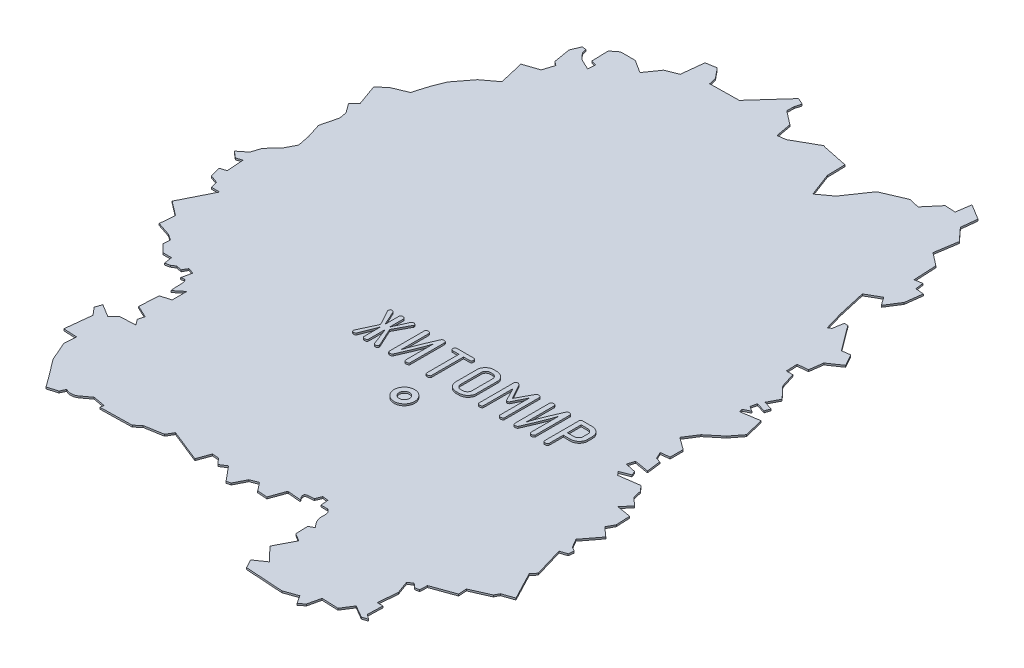
SolidWorks part; units mm, degrees
ref_plane "Спереди" through (0, 0, 0) normal (0, 0, 1) x (1, 0, 0)
ref_plane "Сверху" through (0, 0, 0) normal (0, 1, 0) x (1, 0, 0)
ref_plane "Справа" through (0, 0, 0) normal (1, 0, 0) x (0, 0, -1)
sketch "Эскиз1" plane through (0, 0, 0) normal (0, 1, 0) x (1, 0, 0)
  line B0 (-4547.6465, 8104.5812) -> (-4546.3562, 8148.7162)
  line B1 (-4546.3562, 8148.7162) -> (-4563.2116, 8148.7162)
  line B2 (-4563.2116, 8148.7162) -> (-4558.0351, 8205.1677)
  line B3 (-4558.0351, 8205.1677) -> (-4571.6622, 8242.8055)
  line B4 (-4571.6622, 8242.8055) -> (-4558.0351, 8251.2484)
  line B5 (-4558.0351, 8251.2484) -> (-4546.3562, 8240.8674)
  line B6 (-4546.3562, 8240.8674) -> (-4534.0321, 8242.8055)
  line B7 (-4534.0321, 8242.8055) -> (-4532.7265, 8264.8654)
  line B8 (-4532.7265, 8264.8654) -> (-4465.8915, 8288.8887)
  line B9 (-4465.8915, 8288.8887) -> (-4467.8422, 8312.9018)
  line B10 (-4467.8422, 8312.9018) -> (-4413.3211, 8336.9048)
  line B11 (-4413.3211, 8336.9048) -> (-4406.1913, 8350.5294)
  line B12 (-4406.1913, 8350.5294) -> (-4372.4474, 8362.2159)
  line B13 (-4372.4474, 8362.2159) -> (-4414.6267, 8442.6857)
  line B14 (-4414.6267, 8442.6857) -> (-4402.9274, 8457.6006)
  line B15 (-4402.9274, 8457.6006) -> (-4428.2385, 8543.2722)
  line B16 (-4428.2385, 8543.2722) -> (-4408.1294, 8549.7619)
  line B17 (-4408.1294, 8549.7619) -> (-4406.1913, 8565.3372)
  line B18 (-4406.1913, 8565.3372) -> (-4418.5154, 8572.4695)
  line B19 (-4418.5154, 8572.4695) -> (-4433.4227, 8597.7755)
  line B20 (-4433.4227, 8597.7755) -> (-4395.8078, 8647.1023)
  line B21 (-4395.8078, 8647.1023) -> (-4423.0442, 8671.113)
  line B22 (-4423.0442, 8671.113) -> (-4411.378, 8693.1729)
  line B23 (-4411.378, 8693.1729) -> (-4413.3211, 8734.0618)
  line B24 (-4413.3211, 8734.0618) -> (-4455.508, 8741.2017)
  line B25 (-4455.508, 8741.2017) -> (-4432.1451, 8766.5001)
  line B26 (-4432.1451, 8766.5001) -> (-4455.508, 8789.2153)
  line B27 (-4455.508, 8789.2153) -> (-4460.6921, 8812.5884)
  line B28 (-4460.6921, 8812.5884) -> (-4474.3319, 8828.1586)
  line B29 (-4474.3319, 8828.1586) -> (-4534.0321, 8819.7233)
  line B30 (-4534.0321, 8819.7233) -> (-4543.105, 8830.1119)
  line B31 (-4543.105, 8830.1119) -> (-4513.895, 8841.7756)
  line B32 (-4513.895, 8841.7756) -> (-4519.0994, 8854.1174)
  line B33 (-4519.0994, 8854.1174) -> (-4549.5947, 8860.5843)
  line B34 (-4549.5947, 8860.5843) -> (-4543.105, 8881.3488)
  line B35 (-4543.105, 8881.3488) -> (-4501.576, 8874.2393)
  line B36 (-4501.576, 8874.2393) -> (-4506.7576, 8915.1054)
  line B37 (-4506.7576, 8915.1054) -> (-4520.3974, 8919.0068)
  line B38 (-4520.3974, 8919.0068) -> (-4529.4626, 8939.1261)
  line B39 (-4529.4626, 8939.1261) -> (-4503.5318, 8942.385)
  line B40 (-4503.5318, 8942.385) -> (-4503.5318, 8979.9973)
  line B41 (-4503.5318, 8979.9973) -> (-4539.2061, 9005.9662)
  line B42 (-4539.2061, 9005.9662) -> (-4515.2081, 9043.5989)
  line B43 (-4515.2081, 9043.5989) -> (-4474.3319, 9077.3479)
  line B44 (-4474.3319, 9077.3479) -> (-4449.0208, 9109.7913)
  line B45 (-4449.0208, 9109.7913) -> (-4462.6403, 9166.2504)
  line B46 (-4462.6403, 9166.2504) -> (-4517.1462, 9157.8049)
  line B47 (-4517.1462, 9157.8049) -> (-4519.0994, 9167.5534)
  line B48 (-4519.0994, 9167.5534) -> (-4500.2755, 9176.6314)
  line B49 (-4500.2755, 9176.6314) -> (-4515.2081, 9186.3621)
  line B50 (-4515.2081, 9186.3621) -> (-4510.659, 9203.8805)
  line B51 (-4510.659, 9203.8805) -> (-4483.3997, 9195.4502)
  line B52 (-4483.3997, 9195.4502) -> (-4478.208, 9210.3778)
  line B53 (-4478.208, 9210.3778) -> (-4503.5318, 9218.8233)
  line B54 (-4503.5318, 9218.8233) -> (-4486.656, 9251.2363)
  line B55 (-4486.656, 9251.2363) -> (-4519.0994, 9285.6609)
  line B56 (-4519.0994, 9285.6609) -> (-4532.7265, 9328.4853)
  line B57 (-4532.7265, 9328.4853) -> (-4551.5403, 9328.4853)
  line B58 (-4551.5403, 9328.4853) -> (-4552.8459, 9360.9185)
  line B59 (-4552.8459, 9360.9185) -> (-4522.3354, 9364.1774)
  line B60 (-4522.3354, 9364.1774) -> (-4517.1462, 9403.141)
  line B61 (-4517.1462, 9403.141) -> (-4479.5034, 9429.0591)
  line B62 (-4479.5034, 9429.0591) -> (-4498.3324, 9462.831)
  line B63 (-4498.3324, 9462.831) -> (-4522.3354, 9459.5798)
  line B64 (-4522.3354, 9459.5798) -> (-4576.8463, 9532.8969)
  line B65 (-4576.8463, 9532.8969) -> (-4587.24, 9532.8969)
  line B66 (-4587.24, 9532.8969) -> (-4592.4191, 9502.4016)
  line B67 (-4592.4191, 9502.4016) -> (-4600.8595, 9497.2175)
  line B68 (-4600.8595, 9497.2175) -> (-4616.4348, 9550.4102)
  line B69 (-4616.4348, 9550.4102) -> (-4635.2536, 9633.4809)
  line B70 (-4635.2536, 9633.4809) -> (-4595.6753, 9656.2012)
  line B71 (-4595.6753, 9656.2012) -> (-4578.7996, 9632.1931)
  line B72 (-4578.7996, 9632.1931) -> (-4552.8459, 9673.0541)
  line B73 (-4552.8459, 9673.0541) -> (-4546.3562, 9722.3809)
  line B74 (-4546.3562, 9722.3809) -> (-4570.3592, 9724.3468)
  line B75 (-4570.3592, 9724.3468) -> (-4573.6154, 9748.3498)
  line B76 (-4573.6154, 9748.3498) -> (-4595.6753, 9744.4408)
  line B77 (-4595.6753, 9744.4408) -> (-4598.9291, 9811.3063)
  line B78 (-4598.9291, 9811.3063) -> (-4636.5363, 9840.4782)
  line B79 (-4636.5363, 9840.4782) -> (-4626.1706, 9906.6807)
  line B80 (-4626.1706, 9906.6807) -> (-4660.5546, 9944.3311)
  line B81 (-4660.5546, 9944.3311) -> (-4655.3704, 9990.4067)
  line B82 (-4655.3704, 9990.4067) -> (-4700.1557, 10017.6559)
  line B83 (-4700.1557, 10017.6559) -> (-4706.6352, 9974.8315)
  line B84 (-4706.6352, 9974.8315) -> (-4737.1457, 9976.7746)
  line B85 (-4737.1457, 9976.7746) -> (-4773.4855, 9933.9476)
  line B86 (-4773.4855, 9933.9476) -> (-4803.963, 9941.0799)
  line B87 (-4803.963, 9941.0799) -> (-4872.1137, 9911.8649)
  line B88 (-4872.1137, 9911.8649) -> (-4920.14, 9841.7964)
  line B89 (-4920.14, 9841.7964) -> (-4959.0808, 9813.2443)
  line B90 (-4959.0808, 9813.2443) -> (-4985.0396, 9881.3747)
  line B91 (-4985.0396, 9881.3747) -> (-4986.3426, 9933.9476)
  line B92 (-4986.3426, 9933.9476) -> (-5061.6028, 9949.5331)
  line B93 (-5061.6028, 9949.5331) -> (-5064.8489, 9951.4533)
  line B94 (-5064.8489, 9951.4533) -> (-5134.9453, 9911.8649)
  line B95 (-5134.9453, 9911.8649) -> (-5158.9508, 9908.6238)
  line B96 (-5158.9508, 9908.6238) -> (-5167.3811, 9954.6994)
  line B97 (-5167.3811, 9954.6994) -> (-5206.9619, 9985.2124)
  line B98 (-5206.9619, 9985.2124) -> (-5206.9619, 10005.9642)
  line B99 (-5206.9619, 10005.9642) -> (-5201.7651, 10024.7704)
  line B100 (-5201.7651, 10024.7704) -> (-5220.6042, 10033.2362)
  line B101 (-5220.6042, 10033.2362) -> (-5302.3414, 9942.3779)
  line B102 (-5302.3414, 9942.3779) -> (-5387.3578, 9941.0799)
  line B103 (-5387.3578, 9941.0799) -> (-5392.5724, 9963.1449)
  line B104 (-5392.5724, 9963.1449) -> (-5416.5856, 9992.3498)
  line B105 (-5416.5856, 9992.3498) -> (-5447.0579, 9987.1428)
  line B106 (-5447.0579, 9987.1428) -> (-5454.203, 9922.2662)
  line B107 (-5454.203, 9922.2662) -> (-5488.6098, 9908.6238)
  line B108 (-5488.6098, 9908.6238) -> (-5517.1492, 9867.7425)
  line B109 (-5517.1492, 9867.7425) -> (-5554.8047, 9891.7709)
  line B110 (-5554.8047, 9891.7709) -> (-5597.6291, 9891.7709)
  line B111 (-5597.6291, 9891.7709) -> (-5617.7459, 9876.1728)
  line B112 (-5617.7459, 9876.1728) -> (-5616.448, 9826.8714)
  line B113 (-5616.448, 9826.8714) -> (-5600.8753, 9822.9699)
  line B114 (-5600.8753, 9822.9699) -> (-5602.8057, 9800.905)
  line B115 (-5602.8057, 9800.905) -> (-5635.2618, 9816.4625)
  line B116 (-5635.2618, 9816.4625) -> (-5650.1944, 9833.3611)
  line B117 (-5650.1944, 9833.3611) -> (-5654.0832, 9846.9704)
  line B118 (-5654.0832, 9846.9704) -> (-5665.7773, 9848.9364)
  line B119 (-5665.7773, 9848.9364) -> (-5677.4436, 9821.6745)
  line B120 (-5677.4436, 9821.6745) -> (-5669.0158, 9771.7)
  line B121 (-5669.0158, 9771.7) -> (-5657.3344, 9763.2774)
  line B122 (-5657.3344, 9763.2774) -> (-5667.7077, 9730.8264)
  line B123 (-5667.7077, 9730.8264) -> (-5711.8377, 9715.8988)
  line B124 (-5711.8377, 9715.8988) -> (-5694.9619, 9643.8669)
  line B125 (-5694.9619, 9643.8669) -> (-5735.8661, 9613.3539)
  line B126 (-5735.8661, 9613.3539) -> (-5773.4987, 9564.0449)
  line B127 (-5800.7301, 9483.5878) -> (-5841.6292, 9466.6918)
  line B128 (-5841.6292, 9466.6918) -> (-5868.8834, 9444.6319)
  line B129 (-5868.8834, 9444.6319) -> (-5846.8133, 9383.0038)
  line B130 (-5846.8133, 9383.0038) -> (-5863.6941, 9366.1205)
  line B131 (-5863.6941, 9366.1205) -> (-5843.5672, 9338.2211)
  line B132 (-5843.5672, 9338.2211) -> (-5839.6734, 9316.1612)
  line B133 (-5839.6734, 9316.1612) -> (-5852.0025, 9266.8242)
  line B134 (-5852.0025, 9266.8242) -> (-5838.378, 9224.0125)
  line B135 (-5838.378, 9224.0125) -> (-5831.2431, 9188.3154)
  line B136 (-5831.2431, 9188.3154) -> (-5848.1189, 9155.8593)
  line B137 (-5848.1189, 9155.8593) -> (-5855.2537, 9149.3746)
  line B138 (-5855.2537, 9149.3746) -> (-5876.0182, 9126.6747)
  line B139 (-5876.0182, 9126.6747) -> (-5884.451, 9099.4052)
  line B140 (-5884.451, 9099.4052) -> (-5909.7596, 9079.296)
  line B141 (-5909.7596, 9079.296) -> (-5890.9433, 9063.7106)
  line B142 (-5890.9433, 9063.7106) -> (-5874.0726, 9068.8947)
  line B143 (-5874.0726, 9068.8947) -> (-5870.8341, 9019.5984)
  line B144 (-5870.8341, 9019.5984) -> (-5889.0002, 9013.7437)
  line B145 (-5889.0002, 9013.7437) -> (-5880.5572, 8983.2485)
  line B146 (-5880.5572, 8983.2485) -> (-5857.2146, 8974.8131)
  line B147 (-5857.2146, 8974.8131) -> (-5852.0025, 8954.6963)
  line B148 (-5852.0025, 8954.6963) -> (-5827.9944, 8954.6963)
  line B149 (-5827.9944, 8954.6963) -> (-5874.0726, 8862.5324)
  line B150 (-5874.0726, 8862.5324) -> (-5833.1938, 8831.3971)
  line B151 (-5833.1938, 8831.3971) -> (-5836.4399, 8787.2672)
  line B152 (-5836.4399, 8787.2672) -> (-5795.5409, 8773.6401)
  line B153 (-5795.5409, 8773.6401) -> (-5778.6778, 8761.9535)
  line B154 (-5778.6778, 8761.9535) -> (-5779.9783, 8741.2017)
  line B155 (-5779.9783, 8741.2017) -> (-5757.9082, 8719.1291)
  line B156 (-5757.9082, 8719.1291) -> (-5732.6047, 8719.1291)
  line B157 (-5732.6047, 8719.1291) -> (-5728.7262, 8695.1083)
  line B158 (-5728.7262, 8695.1083) -> (-5715.1016, 8698.3545)
  line B159 (-5715.1016, 8698.3545) -> (-5703.3871, 8705.502)
  line B160 (-5703.3871, 8705.502) -> (-5687.8296, 8702.261)
  line B161 (-5687.8296, 8702.261) -> (-5679.3867, 8717.186)
  line B162 (-5679.3867, 8717.186) -> (-5662.5185, 8710.6912)
  line B163 (-5662.5185, 8710.6912) -> (-5669.0158, 8681.4965)
  line B164 (-5650.1944, 8635.4234) -> (-5624.891, 8656.1879)
  line B165 (-5624.891, 8656.1879) -> (-5624.891, 8613.3584)
  line B166 (-5624.891, 8613.3584) -> (-5654.0832, 8604.9231)
  line B167 (-5654.0832, 8604.9231) -> (-5657.3344, 8548.4487)
  line B168 (-5657.3344, 8548.4487) -> (-5621.6525, 8531.5857)
  line B169 (-5621.6525, 8531.5857) -> (-5626.8417, 8514.0673)
  line B170 (-5626.8417, 8514.0673) -> (-5614.5049, 8497.1865)
  line B171 (-5614.5049, 8497.1865) -> (-5659.2775, 8495.2459)
  line B172 (-5659.2775, 8495.2459) -> (-5677.4436, 8478.3701)
  line B173 (-5677.4436, 8478.3701) -> (-5713.7935, 8500.4351)
  line B174 (-5713.7935, 8500.4351) -> (-5720.2781, 8481.6239)
  line B175 (-5720.2781, 8481.6239) -> (-5701.4542, 8459.5462)
  line B176 (-5701.4542, 8459.5462) -> (-5709.8895, 8382.9804)
  line B177 (-5709.8895, 8382.9804) -> (-5670.9462, 8381.0246)
  line B178 (-5670.9462, 8381.0246) -> (-5672.902, 8345.3351)
  line B179 (-5672.902, 8345.3351) -> (-5648.8813, 8290.8369)
  line B180 (-5648.8813, 8290.8369) -> (-5604.1214, 8231.1265)
  line B181 (-5604.1214, 8231.1265) -> (-5589.1989, 8210.3722)
  line B182 (-5589.1989, 8210.3722) -> (-5559.9813, 8218.8075)
  line B183 (-5559.9813, 8218.8075) -> (-5552.854, 8234.3777)
  line B184 (-5493.1564, 8254.492) -> (-5457.4592, 8247.9972)
  line B185 (-5457.4592, 8247.9972) -> (-5459.3973, 8237.6239)
  line B186 (-5459.3973, 8237.6239) -> (-5367.2486, 8239.572)
  line B187 (-5367.2486, 8239.572) -> (-5350.3779, 8254.492)
  line B188 (-5350.3779, 8254.492) -> (-5297.17, 8263.5877)
  line B189 (-5297.17, 8263.5877) -> (-5285.4784, 8283.6918)
  line B190 (-5285.4784, 8283.6918) -> (-5191.3993, 8246.0567)
  line B191 (-5191.3993, 8246.0567) -> (-5177.7595, 8283.6918)
  line B192 (-5177.7595, 8283.6918) -> (-5158.9508, 8282.3964)
  line B193 (-5158.9508, 8282.3964) -> (-5143.3832, 8264.8654)
  line B194 (-5143.3832, 8264.8654) -> (-5124.5567, 8277.1996)
  line B195 (-5124.5567, 8277.1996) -> (-5088.8646, 8234.3777)
  line B196 (-5088.8646, 8234.3777) -> (-5077.1908, 8237.6239)
  line B197 (-5077.1908, 8237.6239) -> (-5059.6546, 8272.0104)
  line B198 (-5059.6546, 8272.0104) -> (-5037.5769, 8280.4406)
  line B199 (-5037.5769, 8280.4406) -> (-5018.7885, 8256.4427)
  line B200 (-5018.7885, 8256.4427) -> (-4990.2237, 8254.492)
  line B201 (-4990.2237, 8254.492) -> (-4974.6383, 8297.324)
  line B202 (-4974.6383, 8297.324) -> (-4971.4023, 8299.2773)
  line B203 (-4971.4023, 8299.2773) -> (-4933.757, 8296.0134)
  line B204 (-4933.757, 8318.086) -> (-4916.8939, 8319.3941)
  line B205 (-4916.8939, 8319.3941) -> (-4909.7667, 8336.9048)
  line B206 (-4909.7667, 8336.9048) -> (-4892.8884, 8334.9668)
  line B207 (-4892.8884, 8334.9668) -> (-4890.9402, 8312.9018)
  line B208 (-4890.9402, 8312.9018) -> (-4872.1137, 8312.9018)
  line B209 (-4841.6185, 8247.9972) -> (-4856.5359, 8239.572)
  line B210 (-4856.5359, 8239.572) -> (-4855.2329, 8203.8749)
  line B211 (-4855.2329, 8203.8749) -> (-4833.1907, 8190.2529)
  line B212 (-4833.1907, 8190.2529) -> (-4861.7403, 8135.0993)
  line B213 (-4861.7403, 8135.0993) -> (-4822.7894, 8094.2078)
  line B214 (-4822.7894, 8094.2078) -> (-4855.2329, 8072.1403)
  line B215 (-4855.2329, 8072.1403) -> (-4841.6185, 8046.8368)
  line B216 (-4841.6185, 8046.8368) -> (-4731.9565, 8039.6842)
  line B217 (-4731.9565, 8039.6842) -> (-4693.0107, 8053.3215)
  line B218 (-4693.0107, 8053.3215) -> (-4677.4303, 8029.3134)
  line B219 (-4677.4303, 8029.3134) -> (-4662.5104, 8042.9379)
  line B220 (-4662.5104, 8042.9379) -> (-4654.0623, 8079.2828)
  line B221 (-4654.0623, 8079.2828) -> (-4606.0385, 8077.3321)
  line B222 (-4606.0385, 8077.3321) -> (-4585.2842, 8109.7704)
  line B223 (-4585.2842, 8109.7704) -> (-4549.5947, 8089.0059)
  line B224 (-4549.5947, 8089.0059) -> (-4534.0321, 8094.2078)
  line B225 (-4534.0321, 8094.2078) -> (-4547.6465, 8104.5812)
  spline B226 degree 2 poles (-5773.4987, 9564.0449) (-5790.3593, 9523.1509) (-5793.5927, 9508.8862) knots 0.538136 0.538136 0.538136 0.542373 0.542373 0.542373
  spline B227 degree 2 poles (-5793.5927, 9508.8862) (-5797.4865, 9495.2617) (-5800.7301, 9483.5878) knots 0.542373 0.542373 0.542373 0.54661 0.54661 0.54661
  spline B228 degree 2 poles (-5669.0158, 8681.4965) (-5652.1375, 8689.9496) (-5652.1375, 8665.9161) knots 0.70339 0.70339 0.70339 0.707627 0.707627 0.707627
  spline B229 degree 2 poles (-5652.1375, 8665.9161) (-5652.1375, 8641.908) (-5650.1944, 8635.4234) knots 0.707627 0.707627 0.707627 0.711864 0.711864 0.711864
  spline B230 degree 2 poles (-5552.854, 8234.3777) (-5532.7398, 8223.9866) (-5515.8818, 8237.6239) knots 0.79661 0.79661 0.79661 0.800847 0.800847 0.800847
  spline B231 degree 2 poles (-5515.8818, 8237.6239) (-5498.3456, 8251.2484) (-5493.1564, 8254.492) knots 0.800847 0.800847 0.800847 0.805085 0.805085 0.805085
  spline B232 degree 2 poles (-4933.757, 8296.0134) (-4950.6276, 8316.1556) (-4933.757, 8318.086) knots 0.889831 0.889831 0.889831 0.894068 0.894068 0.894068
  spline B233 degree 2 poles (-4872.1137, 8312.9018) (-4858.4841, 8307.6948) (-4860.4322, 8286.9329) knots 0.915254 0.915254 0.915254 0.919492 0.919492 0.919492
  spline B234 degree 2 poles (-4860.4322, 8286.9329) (-4861.7403, 8266.8161) (-4841.6185, 8247.9972) knots 0.919492 0.919492 0.919492 0.923729 0.923729 0.923729
sketch_block_instance "Блок23-1"
sketch_block "Блок23"
extrude "Бобышка-Вытянуть1" add sketch "Эскиз1" along normal blind 5 contours B233 B234 B209 B210 B211 B212 B213 B214 B215 B216 B217 B218 B219 B220 B221 B222 B223 B224 B225 B0 B1 B2 B3 B4 B5 B6 B7 B8 B9 B10 B11 B12 B13 B14 B15 B16 B17 B18 B19 B20 B21 B22 B23 B24 B25 B26 B27 B28 B29 B30 B31 region at (-5121.7109, 0, -9051.1163)
sketch "Эскиз2" plane through (0, 0, 0) normal (0, 1, 0) x (1, 0, 0)
  line L0 (-5285.5851, 8790.8707) -> (-4481.0233, 8790.8707) construction
  circle A0 centre (-5040.9214, 8705.5135) radius 15
  circle A1 centre (-5040.9214, 8705.5135) radius 30
  text T0 "<b>ЖИТОМИР</b>" font "GOST Type AU" height 110
  dimension "D1" = 30
  dimension "D2" = 60
extrude "Бобышка-Вытянуть2" add sketch "Эскиз2" along normal blind 10
scale "Масштаб1" scale about centroid uniform scaling yes scale factor 0.05
